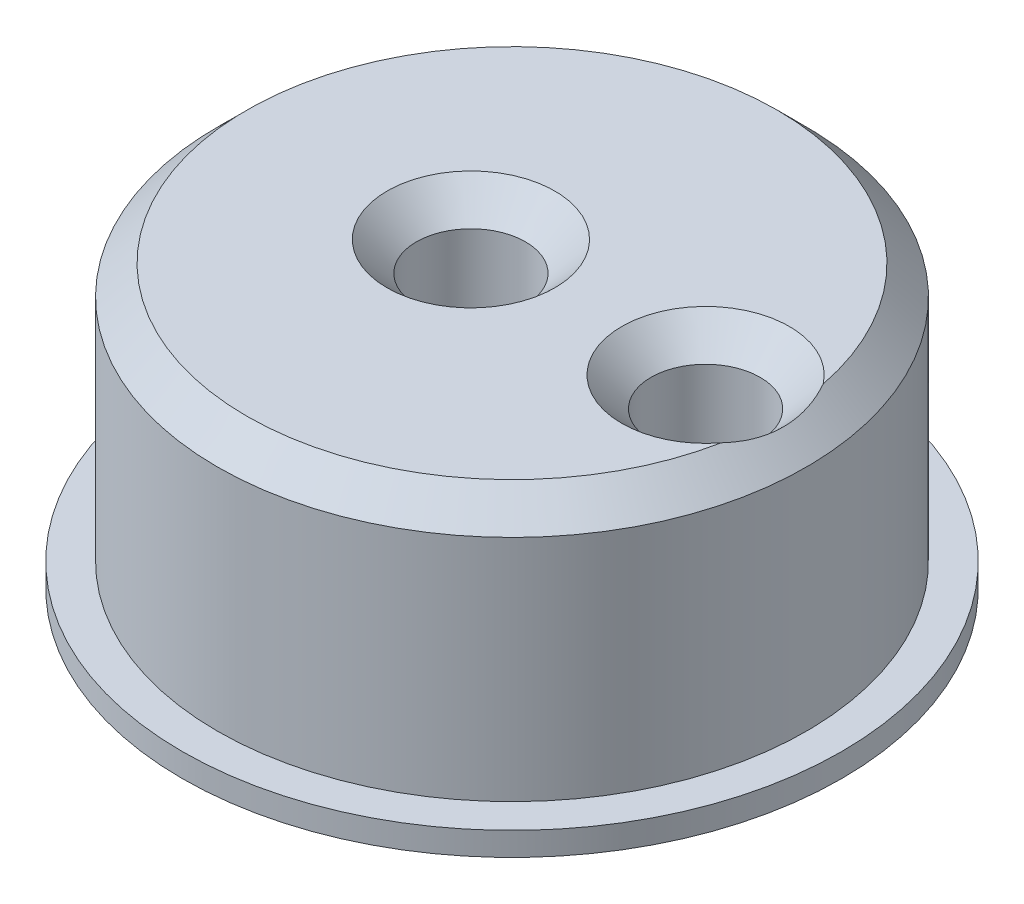
SolidWorks part; units mm, degrees
ref_plane "前视基准面" through (0, 0, 0) normal (0, 0, 1) x (1, 0, 0)
ref_plane "上视基准面" through (0, 0, 0) normal (0, 1, 0) x (1, 0, 0)
ref_plane "右视基准面" through (0, 0, 0) normal (1, 0, 0) x (0, 0, -1)
other "Configuration Table"
sketch "草图1" plane through (0, 0, 0) normal (0, 1, 0) x (1, 0, 0)
  line L0 (1.3, 6.4178) -> (1.3, -6.4114) construction
  line L1 (-5.7349, 0) -> (5.8104, 0) construction
  circle A0 centre (0, 0) radius 5.02
  circle A1 centre (3.3, 0) radius 0.93
  circle A2 centre (-0.7, 0) radius 0.93
  dimension "D1" = 10.04
  dimension "D3" = 4
  dimension "D4" = 1.86
  dimension "D2" = 1.3
extrude "凸台-拉伸1" add sketch "草图1" along normal blind 4.4
sketch "草图3" plane through (0, 0, 0) normal (0, -1, 0) x (1, 0, 0)
  circle A0 centre (3.3, 0) radius 0.93 construction
  circle A1 centre (0, 0) radius 5.02 construction
  circle A3 centre (-0.7, 0) radius 0.93 construction
  circle A4 centre (3.3, 0) radius 0.93
  circle A5 centre (-0.7, 0) radius 0.93
  circle A6 centre (0, 0) radius 5.02 construction
  circle A7 centre (0, 0) radius 5.62
  dimension "D1" = 0.6
extrude "凸台-拉伸2" add sketch "草图3" along normal blind 0.4
chamfer "倒角1" distance 0.5 angle 45 5 edges at (0, 4.4, 5.02) (-0.7, 4.4, -0.93) (3.3, 4.4, 0.93) (-0.7, -0.4, -0.93) (3.3, -0.4, -0.93)
ref_axis "基准轴1" through (0, 3.9, 0) along (0, -1, 0)
sketch "草图2" plane through (0, 0, 0) normal (0, 1, 0) x (1, 0, 0)
  line L0 (-5.9042, 0) -> (6.2358, 0) construction
